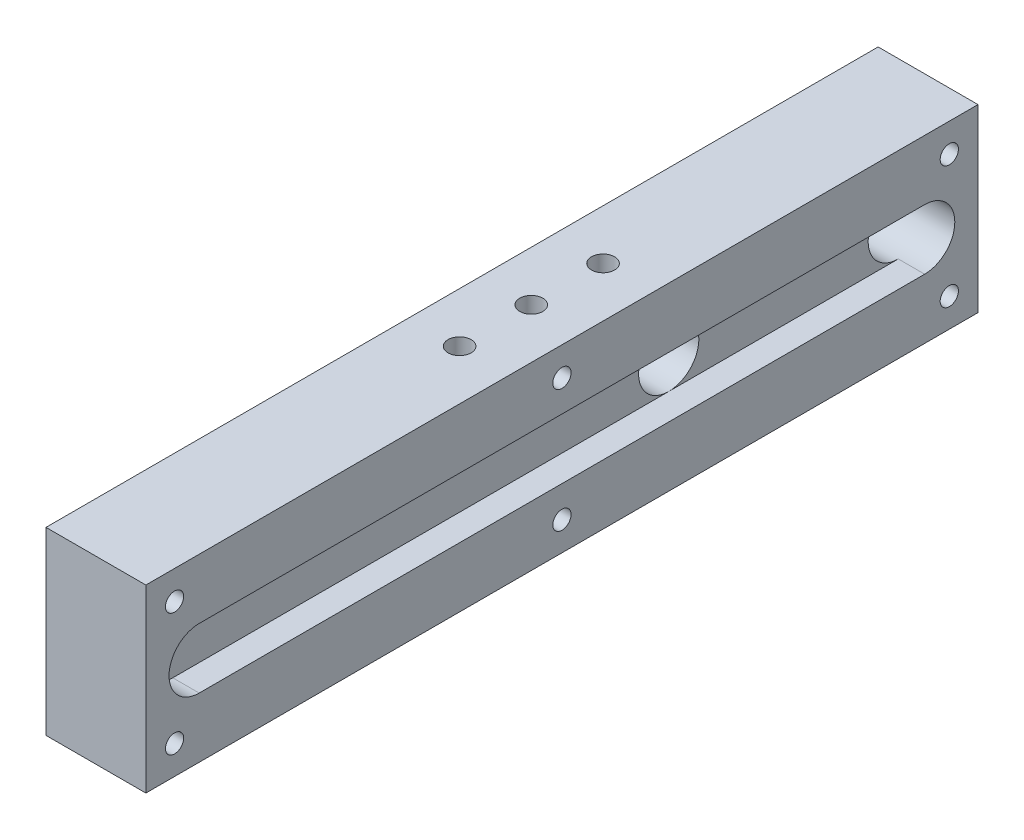
SolidWorks part; units mm, degrees
material "Delrin 2700 NC010, Low Viscosity Acetal Copolymer (SS)"
ref_plane "Front" through (0, 0, 0) normal (0, 0, 1) x (1, 0, 0)
ref_plane "Top" through (0, 0, 0) normal (0, 1, 0) x (1, 0, 0)
ref_plane "Right" through (0, 0, 0) normal (1, 0, 0) x (0, 0, -1)
sketch "Sketch1" plane through (0, 0, 0) normal (1, 0, 0) x (0, 0, -1)
  line L0 (-80.2752, 0) -> (80.2752, 0) construction
  line L1 (92.075, -19.939) -> (-92.075, -19.939)
  line L2 (92.075, -19.939) -> (92.075, 19.939)
  line L3 (92.075, 19.939) -> (-92.075, 19.939)
  line L4 (-92.075, -19.939) -> (-92.075, 19.939)
  line L5 (92.075, -19.939) -> (-92.075, 19.939) construction
  line L6 (92.075, 19.939) -> (-92.075, -19.939) construction
  line L7 (-80.2752, 6.6675) -> (80.2752, 6.6675)
  line L8 (-80.2752, -6.6675) -> (80.2752, -6.6675)
  arc A0 (-80.2752, 6.6675) -> (-80.2752, -6.6675) centre (-80.2752, 0) ccw
  arc A1 (80.2752, -6.6675) -> (80.2752, 6.6675) centre (80.2752, 0) ccw
  point P0 (0, 0)
  point P8 (0, 0)
  dimension "D4" = 13.335
  dimension "D1" = 160.5505
  dimension "D2" = 184.15
  dimension "D3" = 39.878
extrude "Boss-Extrude1" add sketch "Sketch1" along normal blind 22.098
hole_wizard "#10-32 Tapped Hole1" positions "Sketch3" profile "Sketch4" tap size "#10-32" standard "ANSI Inch" end condition through all
sketch "Sketch3" plane through (22.098, 0, 0) normal (1, 0, 0) x (0, 0, -1)
  line L0 (-85.725, 13.589) -> (0, 13.589) construction
  line L1 (0, 13.589) -> (85.725, 13.589) construction
  line L3 (-85.725, 19.939) -> (-85.725, 13.589) construction
  line L4 (92.075, 19.939) -> (-92.075, 19.939) construction
  line L5 (-85.725, 13.589) -> (-85.725, -13.589) construction
  line L6 (-85.725, -13.589) -> (-85.725, -19.939) construction
  line L7 (-92.075, -19.939) -> (92.075, -19.939) construction
  line L8 (-92.075, 19.939) -> (-92.075, -19.939) construction
  point P0 (-85.725, 13.589)
  point P2 (-85.725, -13.589)
  point P4 (0, -13.589)
  point P6 (85.725, -13.589)
  point P8 (85.725, 13.589)
  point P10 (0, 13.589)
  dimension "D1" = 6.35
  dimension "D2" = 6.35
sketch "Sketch4" plane through (22.098, 13.589, 85.725) normal (0, 1, 0) x (0, 0, -1)
  line L0 (0, 0) -> (0, 22.098)
  line L1 (0, 22.098) -> (2.0193, 22.098)
  line L2 (2.0193, 22.098) -> (2.0193, 0)
  line L5 (2.0193, 0) -> (0, 0)
  line L11 (0, -6.35) -> (0, 107.95) construction
  dimension "Thru Tap Drill Dia." = 4.0386
  dimension "Thru Tap Drill Depth" = 22.098
cosmetic thread "Hole Thread1" parameters "D2"=4.826
cosmetic thread "Hole Thread2" parameters "D2"=4.826
cosmetic thread "Hole Thread3" parameters "D2"=4.826
cosmetic thread "Hole Thread4" parameters "D2"=4.826
cosmetic thread "Hole Thread5" parameters "D2"=4.826
cosmetic thread "Hole Thread6" parameters "D2"=4.826
sketch "Sketch5" plane through (0, 0, 0) normal (-1, 0, 0) x (0, 0, 1)
  line L6 (-80.2752, -6.6675) -> (80.2752, -6.6675)
  line L7 (80.2752, 6.6675) -> (-80.2752, 6.6675)
  line L8 (-80.2752, -6.6675) -> (80.2752, -6.6675)
  line L9 (80.2752, 6.6675) -> (-80.2752, 6.6675)
  arc A1 (-80.2752, -6.6675) -> (-80.2752, 6.6675) centre (-80.2752, 0) ccw
  arc A7 (80.2752, -6.6675) -> (80.2752, 6.6675) centre (80.2752, 0) ccw
  arc A8 (-80.2752, 6.6675) -> (-80.2752, -6.6675) centre (-80.2752, 0) ccw
  arc A9 (80.2752, -6.6675) -> (80.2752, 6.6675) centre (80.2752, 0) ccw
  arc A11 (-80.2752, 6.6675) -> (-80.2752, -6.6675) centre (-80.2752, 0) ccw construction
  circle A12 centre (-29.4752, 0) radius 6.6675
  arc M15 (80.2752, 6.6675) -> (80.2752, -6.6675) centre (80.2752, 0) cw
  line M16 (80.2752, -6.6675) -> (-80.2752, -6.6675)
  line M18 (-80.2752, 6.6675) -> (80.2752, 6.6675)
  dimension "D2" = 50.8
  dimension "D1" = 0
extrude "Boss-Extrude2" add sketch "Sketch5" against normal offset from surface (16.256 mm away) 5.842 contours A12 A1 L8 M18 | A12 L9 M16 M15 region at (0, 0, -54.8752) region at (0, 0, 30.6366) up to face at (22.098, 13.589, 83.7057)
hole_wizard "1/4-20 Tapped Hole1" positions "Sketch6" profile "Sketch7" tap size "1/4-20" standard "ANSI Inch" end condition through all
sketch "Sketch6" plane through (0, 19.939, 0) normal (0, 1, 0) x (1, 0, 0)
  point P0 (11.049, -11.6043)
  point P3 (11.049, 4.2707)
  point P6 (11.049, 20.1457)
sketch "Sketch7" plane through (11.049, 19.939, 11.6043) normal (1, 0, 0) x (0, 0, 1)
  line L0 (0, 0) -> (0, 39.878)
  line L1 (0, 39.878) -> (2.5527, 39.878)
  line L2 (2.5527, 39.878) -> (2.5527, 0)
  line L5 (2.5527, 0) -> (0, 0)
  line L11 (0, -6.35) -> (0, 107.95) construction
  dimension "Thru Tap Drill Dia." = 5.1054
  dimension "Thru Tap Drill Depth" = 39.878
cosmetic thread "Hole Thread7" parameters "D2"=6.35
cosmetic thread "Hole Thread8" parameters "D2"=6.35
cosmetic thread "Hole Thread9" parameters "D2"=6.35
